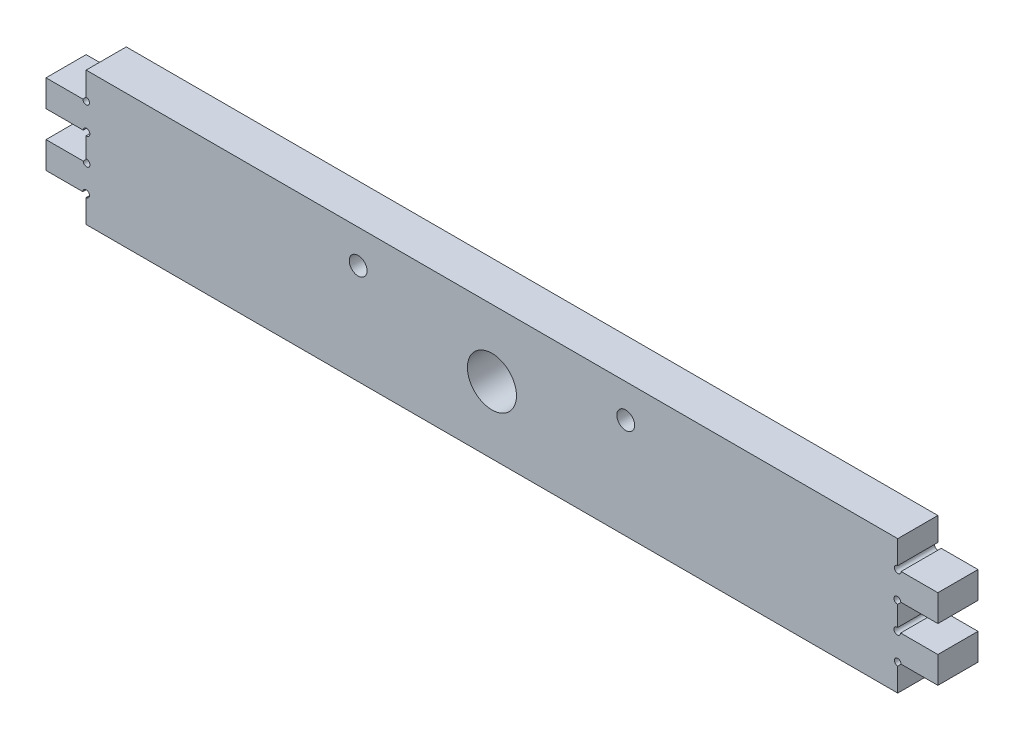
SolidWorks part; units mm, degrees
ref_plane "Front Plane" through (0, 0, 0) normal (0, 0, 1) x (1, 0, 0)
ref_plane "Top Plane" through (0, 0, 0) normal (0, 1, 0) x (1, 0, 0)
ref_plane "Right Plane" through (0, 0, 0) normal (1, 0, 0) x (0, 0, -1)
sketch "Sketch1" plane through (0, 0, 0) normal (0, 0, 1) x (1, 0, 0)
  line L0 (0, -1000) -> (0, 49000) construction
  line L1 (-182, -30) -> (182, -30)
  line L2 (-200, -18) -> (-200, -6)
  line L3 (-182, 30) -> (182, 30)
  line L4 (200, -18) -> (200, -6)
  line L5 (-182, -19.5) -> (-182, -30)
  line L6 (-200, -18) -> (-183.5, -18)
  line L7 (-1000, 0) -> (49000, 0) construction
  line L8 (182, 30) -> (182, 19.5)
  line L9 (200, 18) -> (183.5, 18)
  line L11 (200, -6) -> (183.299, -6)
  line L12 (200, -18) -> (183.5, -18)
  line L13 (182, 4.5) -> (182, -4.5)
  line L14 (200, 6) -> (200, 18)
  line L15 (200, 6) -> (183.299, 6)
  line L16 (182, -19.5) -> (182, -30)
  line L17 (-200, -6) -> (-183.299, -6)
  line L18 (-182, 4.5) -> (-182, -4.5)
  line L19 (-200, 6) -> (-183.299, 6)
  line L20 (-182, 30) -> (-182, 19.5)
  line L21 (-200, 18) -> (-183.5, 18)
  line L22 (-200, 18) -> (-200, 6)
  line L23 (-200, 6) -> (-200, 18)
  line L24 (-200, -6) -> (-200, -18)
  line L25 (-1000, 15) -> (49000, 15) construction
  circle A3 centre (0, 0) radius 4
  circle A4 centre (60, 15) radius 4
  circle A5 centre (-60, 15) radius 4
  arc A6 (182, 19.5) -> (183.5, 18) centre (182, 18) ccw
  arc A7 (183.299, 6) -> (182, 4.5) centre (181.7991, 5.9865) ccw
  arc A8 (182, -4.5) -> (183.299, -6) centre (181.7991, -5.9865) ccw
  arc A9 (183.5, -18) -> (182, -19.5) centre (182, -18) ccw
  arc A10 (-183.5, -18) -> (-182, -19.5) centre (-182, -18) cw
  arc A11 (-182, -4.5) -> (-183.299, -6) centre (-181.7991, -5.9865) cw
  arc A12 (-183.299, 6) -> (-182, 4.5) centre (-181.7991, 5.9865) cw
  arc A13 (-182, 19.5) -> (-183.5, 18) centre (-182, 18) cw
  point P0 (0, 0)
  point P1 (-182, 0)
  point P23 (182, 0)
  point P24 (0, -30)
  point P52 (0, 0)
  point P54 (0, 0)
  point P55 (0, 0)
  dimension "D7" = 3
  dimension "D8" = 12
  dimension "D9" = 12
  dimension "D10" = 60
  dimension "D11" = 16.5
  dimension "D4" = 8
  dimension "D13" = 364
  dimension "D14" = 60
  dimension "D15" = 18
  dimension "D2" = 12
  dimension "D3" = 18
  dimension "D6" = 400
  dimension "D12" = 18
  dimension "D16" = 15
  dimension "D5" = 12
extrude "Boss-Extrude1" add sketch "Sketch1" along normal blind 18 contours L21 L22 L19 L18 L17 L2 L6 L5 L1 L16 L12 L4 L11 L13 L14 L9 L8 L3 L20 A5 region at (-177.9553, -24.75, 0)
sketch "Sketch2" plane through (0, 0, 18) normal (0, 0, 1) x (1, 0, 0)
  line L0 (-1000, 0) -> (49000, 0) construction
  line L1 (0, -1000) -> (0, 49000) construction
  circle A0 centre (0, 0) radius 11
  dimension "D1" = 22
extrude "Cut-Extrude1" cut sketch "Sketch2" against normal up to next
